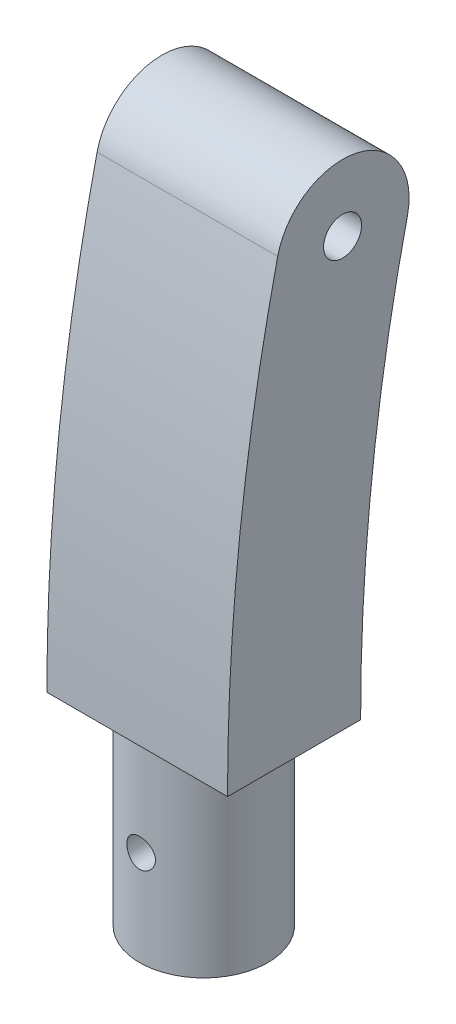
SolidWorks part; units mm, degrees
ref_plane "Front Plane" through (0, 0, 0) normal (0, 0, 1) x (1, 0, 0)
ref_plane "Top Plane" through (0, 0, 0) normal (0, 1, 0) x (1, 0, 0)
ref_plane "Right Plane" through (0, 0, 0) normal (1, 0, 0) x (0, 0, -1)
sketch "Sketch1" plane through (0, 0, 0) normal (1, 0, 0) x (0, 0, -1)
  line L1 (0, 0) -> (400, 0) construction
  line L2 (400, 0) -> (400, 90) construction
  line L3 (400, 90) -> (10.196, 90) construction
  arc A0 (10.196, 90) -> (0, 0) centre (400, 0.2619) ccw
  dimension "D2" = 400
  dimension "D3" = 90
sketch "Sketch2" plane through (0, 0, 0) normal (0, 1, 0) x (1, 0, 0)
  line L1 (-19, -14) -> (19, -14)
  line L2 (-19, -14) -> (-19, 14)
  line L3 (-19, 14) -> (19, 14)
  line L4 (19, -14) -> (19, 14)
  line L5 (-19, -14) -> (19, 14) construction
  line L6 (-19, 14) -> (19, -14) construction
  point P0 (0, 0)
  dimension "D1" = 38
  dimension "D2" = 28
sweep "Sweep1" add profiles "Sketch2" path "Sketch1"
sketch "Sketch3" plane through (0, 0, 0) normal (0, -1, 0) x (1, 0, 0)
  circle A0 centre (0, 0) radius 13.5
  dimension "D1" = 27
extrude "Boss-Extrude1" add sketch "Sketch3" along normal blind 40
sketch "Sketch4" plane through (19, 0, 0) normal (1, 0, 0) x (0, 0, -1)
  line L0 (-3.4451, 93.1498) -> (23.8371, 86.8502) construction
  line L1 (-3.4451, 93.1498) -> (23.8371, 86.8502)
  arc A0 (23.8371, 86.8502) -> (-3.4451, 93.1498) centre (10.196, 90) ccw
extrude "Boss-Extrude2" add sketch "Sketch4" against normal up to surface (38 mm away) up to face at (-19, 45.1448, -3.8202)
sketch "Sketch5" plane through (19, 0, 0) normal (1, 0, 0) x (0, 0, -1)
  circle A0 centre (10.196, 90) radius 4
  dimension "D1" = 8
extrude "Cut-Extrude1" cut sketch "Sketch5" against normal up to next
ref_plane "Plane1" through (0, 0, 13.5) normal (0, 0, 1) x (1, 0, 0)
sketch "Sketch6" plane through (0, 0, 13.5) normal (0, 0, 1) x (1, 0, 0)
  line L0 (-13.5, -40) -> (13.5, -40) construction
  circle A0 centre (0, -20) radius 3
  dimension "D1" = 6
  dimension "D2" = 20
extrude "Cut-Extrude2" cut sketch "Sketch6" against normal up to next
